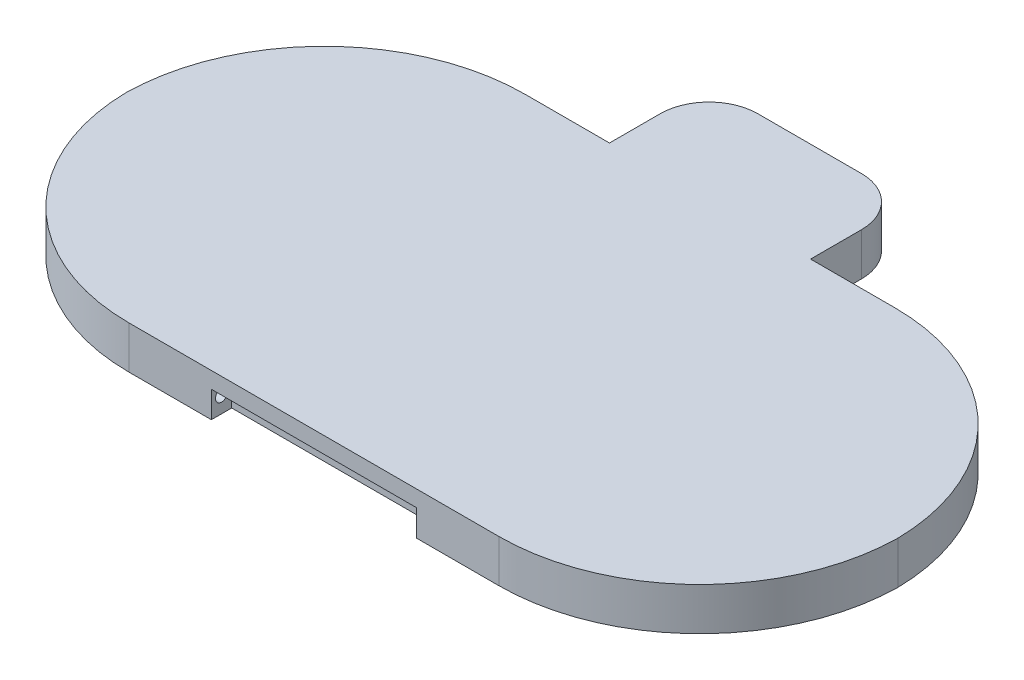
SolidWorks part; units mm, degrees
ref_plane "Front Plane" through (0, 0, 0) normal (0, 0, 1) x (1, 0, 0)
ref_plane "Top Plane" through (0, 0, 0) normal (0, 1, 0) x (1, 0, 0)
ref_plane "Right Plane" through (0, 0, 0) normal (1, 0, 0) x (0, 0, -1)
sketch "Sketch1" plane through (0, 0, 0) normal (0, 1, 0) x (1, 0, 0)
  line L1 (190, 97.5) -> (-190, 97.5)
  line L2 (190, 97.5) -> (190, -97.5)
  line L3 (190, -97.5) -> (-190, -97.5)
  line L4 (-190, 97.5) -> (-190, -97.5)
  line L5 (190, 97.5) -> (-190, -97.5) construction
  line L6 (190, -97.5) -> (-190, 97.5) construction
  point P0 (0, 0)
  dimension "D1" = 380
  dimension "D2" = 195
extrude "Boss-Extrude1" add sketch "Sketch1" along normal blind 21
fillet "Fillet1" radius 99 4 edges at (-190, 10.5, 97.5) (-190, 10.5, -97.5) (190, 10.5, -97.5) (190, 10.5, 97.5)
sketch "Sketch2" plane through (0, 0, 0) normal (0, -1, 0) x (1, 0, 0)
  line L0 (-91, 97.5) -> (91, 97.5) construction
  line L1 (50.5, 107.5) -> (-50.5, 107.5)
  line L2 (50.5, 107.5) -> (50.5, 87.5)
  line L3 (50.5, 87.5) -> (-50.5, 87.5)
  line L4 (-50.5, 107.5) -> (-50.5, 87.5)
  line L5 (50.5, 107.5) -> (-50.5, 87.5) construction
  line L6 (50.5, 87.5) -> (-50.5, 107.5) construction
  point P0 (0, 97.5)
  dimension "D1" = 101
  dimension "D2" = 10
extrude "Cut-Extrude1" cut sketch "Sketch2" against normal blind 13
fillet "Fillet2" radius 4 1 edges at (0, 13, 87.5)
sketch "Sketch3" plane through (-50.5, 0, 0) normal (1, 0, 0) x (0, 0, -1)
  line L0 (-97.5, 0) -> (-97.5, 13) construction
  line L1 (-97.5, 0) -> (-87.5, 0) construction
  circle A0 centre (-92.5, 8) radius 3
  dimension "D2" = 6
  dimension "D1" = 5
  dimension "D3" = 8
extrude "Cut-Extrude2" cut sketch "Sketch3" against normal blind 10 and the other way blind 110
sketch "Sketch4" plane through (0, 0, -97.5) normal (0, 0, -1) x (-1, 0, 0)
  line L0 (-91, 21) -> (91, 21) construction
  line L1 (-49.5, 21) -> (49.5, 21)
  line L2 (-49.5, 21) -> (-49.5, 0)
  line L3 (-49.5, 0) -> (49.5, 0)
  line L4 (49.5, 21) -> (49.5, 0)
  line L5 (-91, 0) -> (91, 0) construction
  point P8 (0, 21)
  dimension "D1" = 0
  dimension "D2" = 99
  dimension "D3" = 0
extrude "Boss-Extrude2" add sketch "Sketch4" along normal blind 49
fillet "Fillet3" radius 24 2 edges at (-49.5, 10.5, -146.5) (49.5, 10.5, -146.5)
